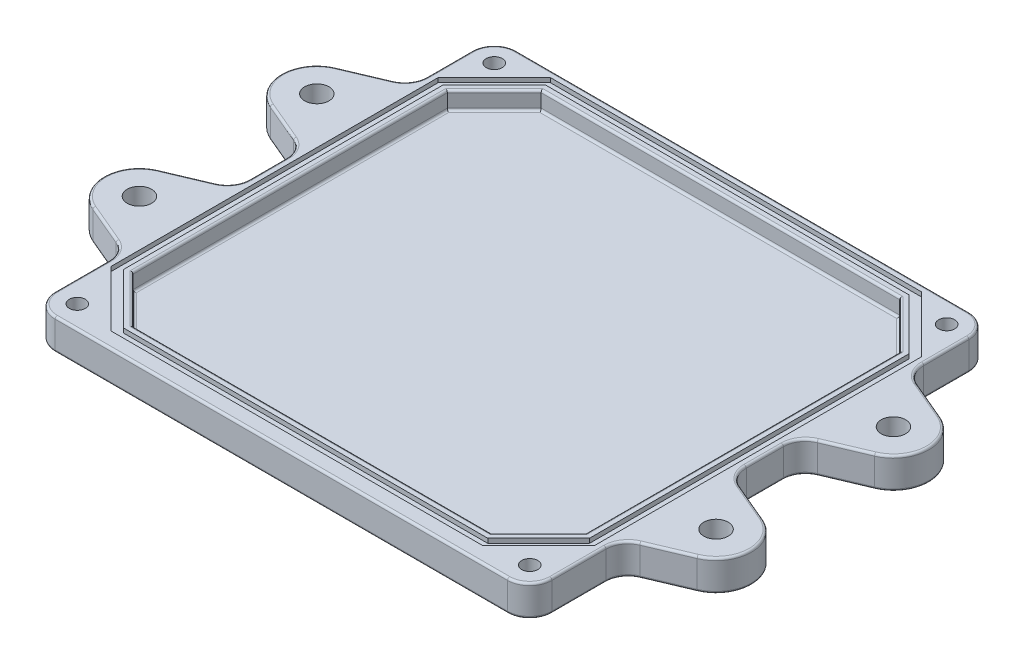
SolidWorks part; units mm, degrees
material "ABS"
ref_plane "Front Plane" through (0, 0, 0) normal (0, 0, 1) x (1, 0, 0)
ref_plane "Top Plane" through (0, 0, 0) normal (0, 1, 0) x (1, 0, 0)
ref_plane "Right Plane" through (0, 0, 0) normal (1, 0, 0) x (0, 0, -1)
ref_plane "PCB Top Plane" through (0, 10, 0) normal (0, 1, 0) x (1, 0, 0)
sketch "PCB Sketch" plane through (0, 10, 0) normal (0, 1, 0) x (1, 0, 0)
  line L0 (-50, 35) -> (-50, -35) construction
  line L1 (-50, -35) -> (-40, -45) construction
  line L2 (-40, -45) -> (40, -45) construction
  line L3 (40, -45) -> (50, -35) construction
  line L4 (50, -35) -> (50, 35) construction
  line L5 (50, 35) -> (40, 45) construction
  line L6 (40, 45) -> (-40, 45) construction
  line L7 (-40, 45) -> (-50, 35) construction
  line L8 (-29.625, -49.5) -> (29.625, -49.5) construction
  point P4 (-40, 35)
  point P9 (40, 35)
  point P10 (40, -35)
  point P11 (-40, -35)
  point P12 (0, 12)
  point P13 (0, 45)
  point P15 (50, 0)
  point P16 (0, -40)
  point P19 (0, -49.5)
  dimension "D1" = 100
  dimension "D2" = 90
  dimension "D3" = 10
  dimension "D4" = 57
  dimension "D5" = 5
  dimension "D6" = 59.25
  dimension "D7" = 9.5
ref_plane "Connector Front Plane" through (0, 0, 49.5) normal (0, 0, 1) x (1, 0, 0)
sketch "Connector Front Sketch" plane through (0, 0, 49.5) normal (0, 0, 1) x (1, 0, 0)
  line L0 (-29.605, 45.26) -> (29.605, 45.26) construction
  line L1 (29.605, 45.26) -> (29.605, 10) construction
  line L2 (29.605, 10) -> (-29.605, 10) construction
  line L3 (-29.605, 10) -> (-29.605, 45.26) construction
  line L4 (-29.625, 10) -> (29.625, 10) construction
  line L5 (-24.65, 27.63) -> (24.65, 27.63) construction
  point P6 (0, 45.26)
  point P11 (0, 27.63)
  point P12 (29.605, 27.63)
  point P14 (-24.65, 27.63)
  point P15 (24.65, 27.63)
  dimension "D1" = 35.26
  dimension "D2" = 59.21
  dimension "D3" = 49.3
sketch "Connector Right Sketch" plane through (0, 0, 0) normal (1, 0, 0) x (0, 0, -1)
  line L0 (-49.5, 10) -> (-49.5, 45.26) construction
  line L1 (-49.5, 10) -> (-49.5, 45.26) construction
  line L2 (-49.5, 45.26) -> (-34.01, 45.26) construction
  line L3 (-34.01, 45.26) -> (-34.01, 10) construction
  line L4 (-34.01, 10) -> (-49.5, 10) construction
  line L5 (-49.5, 38.755) -> (-64.11, 38.755) construction
  line L6 (-64.11, 38.755) -> (-64.11, 16.505) construction
  line L7 (-64.11, 16.505) -> (-49.5, 16.505) construction
  line L8 (-64.11, 27.63) -> (-34.01, 27.63) construction
  line L9 (-35, 10) -> (-45, 10) construction
  line L10 (-49.5, 45.26) -> (-49.5, 10) construction
  point P12 (-34.01, 27.63)
  point P15 (-64.11, 27.63)
  dimension "D1" = 15.49
  dimension "D2" = 14.61
  dimension "D3" = 22.25
sketch "Base Sketch" plane through (0, 0, 0) normal (0, 1, 0) x (1, 0, 0)
  line L0 (40, 45) -> (-40, 45) construction
  line L1 (-56, 51) -> (56, 51)
  line L2 (-56, 51) -> (-56, -53)
  line L3 (-56, -53) -> (56, -53)
  line L4 (56, 51) -> (56, -53)
  line L5 (-50, 35) -> (-50, -35) construction
  line L6 (-29.625, -49.5) -> (29.625, -49.5) construction
  point P8 (0, 51)
  dimension "D1" = 6
  dimension "D2" = 6
  dimension "D3" = 3.5
extrude "Base" add sketch "Base Sketch" along normal blind 7
fillet "Corner Fillet" radius 5 4 edges at (56, 3.5, -51) (56, 3.5, 53) (-56, 3.5, 53) (-56, 3.5, -51)
sketch "Rear Left Mounting Flange Sketch" plane through (0, 0, 0) normal (0, 1, 0) x (1, 0, 0)
  line L0 (-68.1201, 12.6335) -> (-56, 7.5)
  line L1 (-56, 46) -> (-56, -48) construction
  line L2 (-68.1201, 27.3665) -> (-56, 32.5)
  line L3 (-56, 32.5) -> (-56, 7.5)
  arc A0 (-68.1201, 27.3665) -> (-68.1201, 12.6335) centre (-65, 20) ccw
  circle A1 centre (-65, 20) radius 2.75
  dimension "D1" = 8
  dimension "D5" = 5.5
  dimension "D2" = 9
  dimension "D3" = 20
  dimension "D4" = 25
extrude "Rear Left Mounting Flange" add sketch "Rear Left Mounting Flange Sketch" along normal up to surface (7 mm away) up to face at (0, 7, 1)
mirror "Rear Right Mounting Flange" about plane through (0, 0, 0) normal (1, 0, 0) of "Rear Left Mounting Flange"
mirror "Front Mounting Flanges" about plane through (0, 0, 0) normal (0, 0, 1) of "Rear Right Mounting Flange", "Rear Left Mounting Flange"
fillet "Mounting Flange Fillet" radius 5 8 edges at (-56, 3.5, -32.5) (-56, 3.5, -7.5) (-56, 3.5, 7.5) (-56, 3.5, 32.5) (56, 3.5, -32.5) (56, 3.5, -7.5) (56, 3.5, 7.5) (56, 3.5, 32.5)
fillet "Top and Bottom Fillet" radius 0.5 64 edges at (-54.5355, 0, 51.5355) (-56, 0, 41.9061) (-56.8316, 0, 33.0509) (-63.585, 0, 29.2873) (-73, 0, 20) (-63.585, 0, 10.7127) (-56.8316, 0, 6.9491) (-56, 0, 0) (-56.8316, 0, -6.9491) (-63.585, 0, -10.7127) (-73, 0, -20) (-63.585, 0, -29.2873) (-56.8316, 0, -33.0509) (-56, 0, -40.9061) (-54.5355, 0, -49.5355) (0, 0, -51) (54.5355, 0, -49.5355) (56, 0, -40.9061) (56.8316, 0, -33.0509) (63.585, 0, -29.2873) (73, 0, -20) (63.585, 0, -10.7127) (56.8316, 0, -6.9491) (56, 0, 0) (56.8316, 0, 6.9491) (63.585, 0, 10.7127) (73, 0, 20) (63.585, 0, 29.2873) (56.8316, 0, 33.0509) (56, 0, 41.9061) (54.5355, 0, 51.5355) (-54.5355, 7, 51.5355) (-56, 7, 41.9061) (-56.8316, 7, 33.0509) (-63.585, 7, 29.2873) (-73, 7, 20) (-63.585, 7, 10.7127) (-56.8316, 7, 6.9491) (-56, 7, 0) (-56.8316, 7, -6.9491) (-63.585, 7, -10.7127) (-73, 7, -20) (-63.585, 7, -29.2873) (-56.8316, 7, -33.0509) (-56, 7, -40.9061) (-54.5355, 7, -49.5355) (0, 7, -51) (54.5355, 7, -49.5355) (56, 7, -40.9061) (56.8316, 7, -33.0509) (63.585, 7, -29.2873) (73, 7, -20) (63.585, 7, -10.7127) (56.8316, 7, -6.9491) (56, 7, 0) (56.8316, 7, 6.9491) (63.585, 7, 10.7127) (73, 7, 20) (63.585, 7, 29.2873) (56.8316, 7, 33.0509) (56, 7, 41.9061) (54.5355, 7, 51.5355) (0, 0, 53) (0, 7, 53)
sketch "PCB Pocket Sketch" plane through (0, 7, 0) normal (0, 1, 0) x (1, 0, 0)
  line L16 (-40.4142, 46) -> (-51, 35.4142)
  line L17 (-51, 35.4142) -> (-51, -35.4142)
  line L18 (-51, -35.4142) -> (-40.4142, -46)
  line L19 (-40.4142, -46) -> (40.4142, -46)
  line L20 (40.4142, -46) -> (51, -35.4142)
  line L21 (51, -35.4142) -> (51, 35.4142)
  line L22 (51, 35.4142) -> (40.4142, 46)
  line L23 (40.4142, 46) -> (-40.4142, 46)
  line L24 (-40.4142, 46) -> (-51, 35.4142)
  line L25 (-51, 35.4142) -> (-51, -35.4142)
  line L26 (-51, -35.4142) -> (-40.4142, -46)
  line L27 (-40.4142, -46) -> (40.4142, -46)
  line L28 (40.4142, -46) -> (51, -35.4142)
  line L29 (51, -35.4142) -> (51, 35.4142)
  line L30 (51, 35.4142) -> (40.4142, 46)
  line L31 (40.4142, 46) -> (-40.4142, 46)
  dimension "D1" = 1
extrude "PCB Pocket" cut sketch "PCB Pocket Sketch" against normal blind 4
fillet "Inside Fillet" radius 0.5 16 edges at (45.7071, 3, 40.7071) (45.7071, 7, 40.7071) (51, 3, 0) (51, 7, 0) (0, 7, 46) (0, 3, 46) (-45.7071, 3, 40.7071) (-45.7071, 7, 40.7071) (-51, 7, 0) (-45.7071, 7, -40.7071) (0, 7, -46) (45.7071, 7, -40.7071) (45.7071, 3, -40.7071) (0, 3, -46) (-51, 3, 0) (-45.7071, 3, -40.7071)
sketch "Sealing Channel Sketch" plane through (0, 7, 0) normal (0, 1, 0) x (1, 0, 0)
  line L8 (-41.864, 49.5) -> (-54.5, 36.864)
  line L9 (-54.5, 36.864) -> (-54.5, -36.864)
  line L10 (-54.5, -36.864) -> (-41.864, -49.5)
  line L11 (-41.864, -49.5) -> (41.864, -49.5)
  line L12 (41.864, -49.5) -> (54.5, -36.864)
  line L13 (54.5, -36.864) -> (54.5, 36.864)
  line L14 (54.5, 36.864) -> (41.864, 49.5)
  line L15 (41.864, 49.5) -> (-41.864, 49.5)
  line L16 (-41.0355, 47.5) -> (-52.5, 36.0355)
  line L17 (-52.5, 36.0355) -> (-52.5, -36.0355)
  line L18 (-52.5, -36.0355) -> (-41.0355, -47.5)
  line L19 (-41.0355, -47.5) -> (41.0355, -47.5)
  line L20 (41.0355, -47.5) -> (52.5, -36.0355)
  line L21 (52.5, -36.0355) -> (52.5, 36.0355)
  line L22 (52.5, 36.0355) -> (41.0355, 47.5)
  line L23 (41.0355, 47.5) -> (-41.0355, 47.5)
  line L24 (-41.0355, 47.5) -> (-52.5, 36.0355)
  line L25 (-52.5, 36.0355) -> (-52.5, -36.0355)
  line L26 (-52.5, -36.0355) -> (-41.0355, -47.5)
  line L27 (-41.0355, -47.5) -> (41.0355, -47.5)
  line L28 (41.0355, -47.5) -> (52.5, -36.0355)
  line L29 (52.5, -36.0355) -> (52.5, 36.0355)
  line L30 (52.5, 36.0355) -> (41.0355, 47.5)
  line L31 (41.0355, 47.5) -> (-41.0355, 47.5)
  dimension "D1" = 1.5
  dimension "D2" = 2
extrude "Sealing Channel" cut sketch "Sealing Channel Sketch" against normal blind 1
hole_wizard "CBORE for M3 Hex Head Machine Screw1" positions "Enclosure Mounting Hole Sketch" profile "M3 Countersunk Low Profile Hole Sketch" counterbore size "M3" standard "ANSI Metric"
sketch "Enclosure Mounting Hole Sketch" plane through (0, 0, 0) normal (0, -1, 0) x (-1, 0, 0)
  line L8 (56, 51) -> (-56, 51)
  line L9 (-56, 51) -> (-56, -53)
  line L10 (-56, -53) -> (56, -53)
  line L11 (56, -53) -> (56, 51)
  line L12 (56, 51) -> (-56, 51) construction
  line L13 (-56, 51) -> (-56, -53) construction
  line L14 (-56, -53) -> (56, -53) construction
  line L15 (56, -53) -> (56, 51) construction
  point P0 (51, -48)
  point P2 (51, 46)
  point P4 (-51, 46)
  point P6 (-51, -48)
  dimension "D2" = 5
  dimension "D3" = 5
  dimension "D4" = 5
  dimension "D5" = 5
  dimension "D1" = 0
sketch "M3 Countersunk Low Profile Hole Sketch" plane through (-51, 0, 48) normal (1, 0, 0) x (0, 0, -1)
  line L0 (0, 0) -> (0, 8.0815)
  line L1 (0, 8.0815) -> (1.8, 7)
  line L2 (1.8, 7) -> (1.8, 2)
  line L3 (1.8, 2) -> (3, 2)
  line L4 (3, 2) -> (3, 0)
  line L5 (3, 0) -> (0, 0)
  line L10 (0, 8.0815) -> (-1.8, 7) construction
  line L11 (0, -6.35) -> (0, 107.95) construction
  dimension "Hole Dia." = 3.6
  dimension "Hole Depth" = 7
  dimension "C'Bore Dia." = 6
  dimension "C'Bore Depth" = 2
  dimension "Drill Angle" = 118
ref_axis "Enclosure Rear Left Axis" through (-51, 30.7147, -46) along (0, -1, 0)
ref_axis "Enclosure Front Left Axis" through (-51, 42.5655, 48) along (0, -1, 0)
ref_axis "Enclosure Front Right Axis" through (51, 44.5272, 48) along (0, -1, 0)
ref_axis "Enclosure Rear Right Axis" through (51, 56.0968, -46) along (0, -1, 0)
ref_plane "Enclosure Bottom Plane" through (0, 7, 0) normal (0, 1, 0) x (1, 0, 0)
ref_plane "Enclosure Mounting Screw Plane" through (0, 2, 0) normal (0, -1, 0) x (-1, 0, 0)
